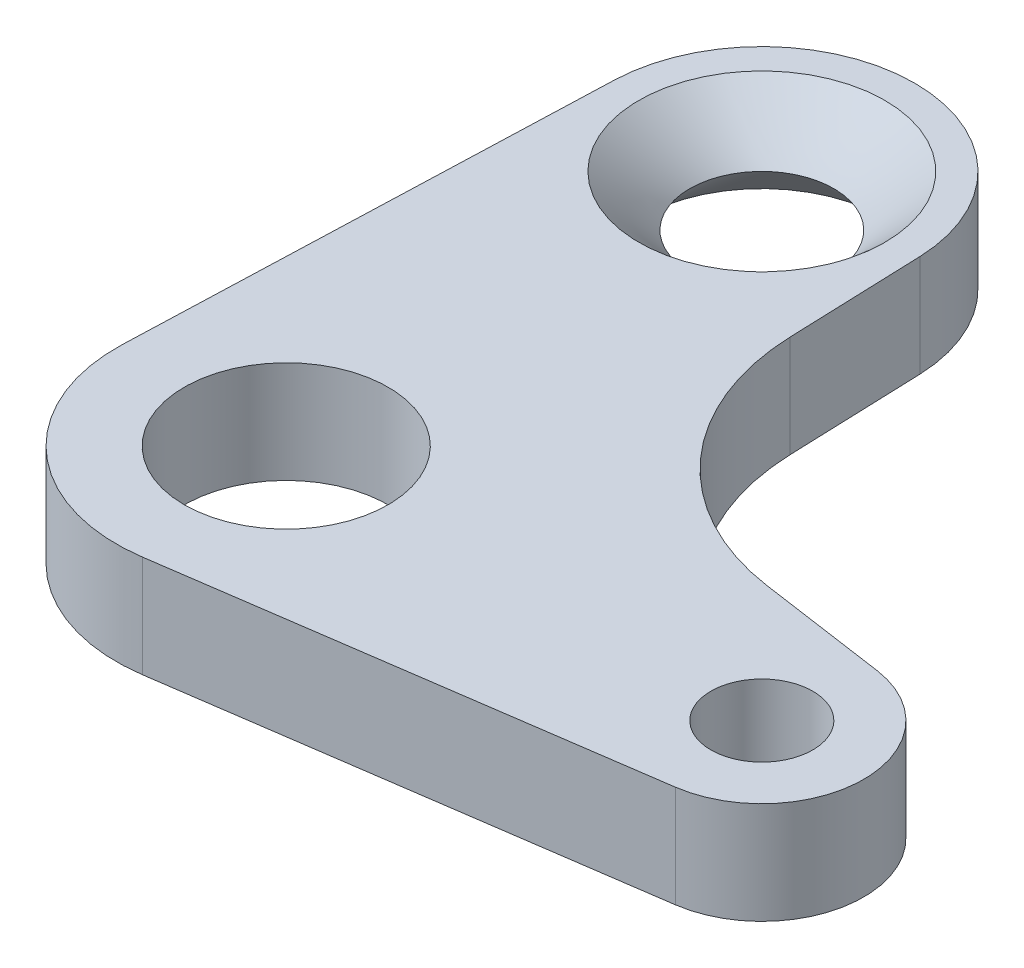
SolidWorks part; units mm, degrees
ref_plane "Front Plane" through (0, 0, 0) normal (0, 0, 1) x (1, 0, 0)
ref_plane "Top Plane" through (0, 0, 0) normal (0, 1, 0) x (1, 0, 0)
ref_plane "Right Plane" through (0, 0, 0) normal (1, 0, 0) x (0, 0, -1)
sketch "Sketch1" plane through (0, 0, 0) normal (0, 1, 0) x (1, 0, 0)
  line L0 (-34.6817, 0) -> (40.0134, 0) construction
  line L1 (0, 34.2279) -> (0, -27.1843) construction
  line L2 (-4.4971, 14.1607) -> (-4.9968, 0.1786)
  line L3 (0.7143, -4.9487) -> (14.4286, -2.9692)
  line L4 (4.4971, 14.1607) -> (4.8477, 4.3521)
  line L5 (14.4286, 2.9692) -> (4.8477, 4.3521)
  arc A2 (-4.9968, 0.1786) -> (0.7143, -4.9487) centre (0, 0) ccw
  arc A3 (4.4971, 14.1607) -> (-4.4971, 14.1607) centre (0, 14) ccw
  arc A4 (14.4286, -2.9692) -> (14.4286, 2.9692) centre (14, 0) ccw
  circle A5 centre (0, 0) radius 3
  circle A6 centre (14, 0) radius 1.5
  dimension "D3" = 6
  dimension "D4" = 3
  dimension "D5" = 10
  dimension "D6" = 9
  dimension "D7" = 6
  dimension "D1" = 14
  dimension "D2" = 14
extrude "Boss-Extrude1" add sketch "Sketch1" along normal mid plane 3
sketch "Sketch2" plane through (0, 0, 0) normal (0, 1, 0) x (1, 0, 0)
  circle A0 centre (0, 14) radius 3 construction
ref_plane "Plane1" through (0, 0, 0) normal (0.7071, 0.7071, 0) x (0.7071, -0.7071, 0)
sketch "Sketch4" plane through (0, 0, 0) normal (0, 1, 0) x (1, 0, 0)
  circle A1 centre (0, 14) radius 2.1213
  dimension "D1" = 4.2426
sketch "Sketch5" plane through (0, 1.5, 0) normal (0, 1, 0) x (1, 0, 0)
  circle A0 centre (0, 14) radius 3.6213
  dimension "D1" = 7.2426
loft "Cut-Loft1" cut profiles "Sketch5", "Sketch4" connector at (-3.0515, 1.5, -15.95) connector at (-1.1724, 0, -15.7679)
fillet "Fillet1" radius 7 1 edges at (4.8477, 0, -4.3521)
mirror "Mirror1" about plane through (0, 0, 0) normal (0, 1, 0) of "Cut-Loft1"
